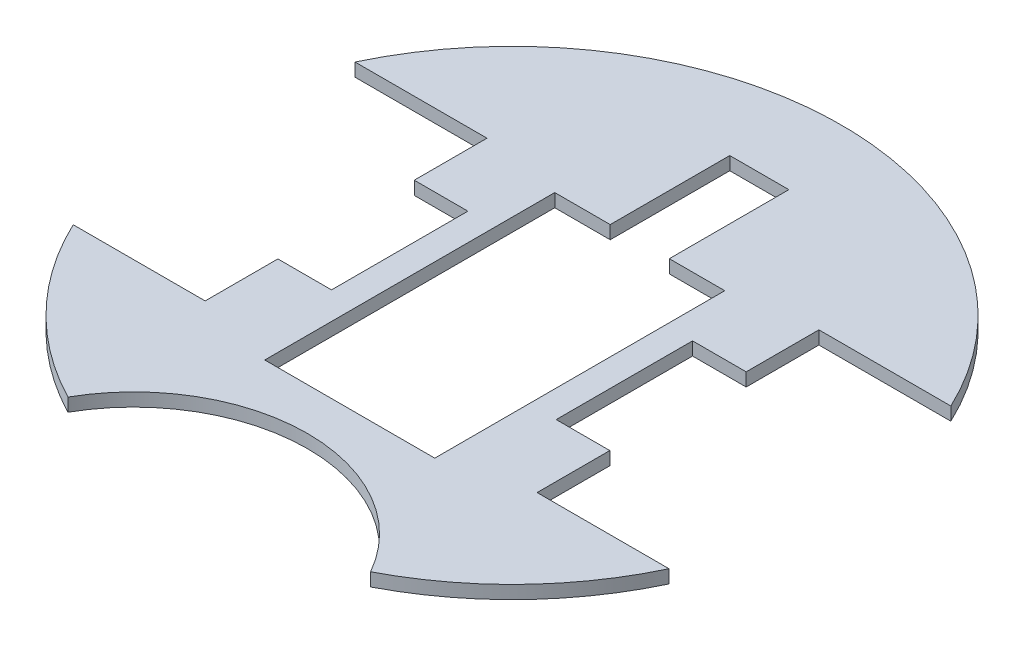
SolidWorks part; units mm, degrees
ref_plane "Front Plane" through (0, 0, 0) normal (0, 0, 1) x (1, 0, 0)
ref_plane "Top Plane" through (0, 0, 0) normal (0, 1, 0) x (1, 0, 0)
ref_plane "Right Plane" through (0, 0, 0) normal (1, 0, 0) x (0, 0, -1)
sketch "Sketch1" plane through (0, 0, 0) normal (0, 1, 0) x (1, 0, 0)
  line L0 (0, -83.2398) -> (-33.2911, -64.4046) construction
  line L1 (0, -83.2398) -> (0, 0) construction
  arc A0 (33.2911, -64.4046) -> (-33.2911, -64.4046) centre (0, 0) ccw
  arc A1 (33.2911, -64.4046) -> (-33.2911, -64.4046) centre (0, -83.2398) ccw
  dimension "D1" = 145
  dimension "D2" = 76.5
  dimension "D3" = 60.5
extrude "Boss-Extrude1" add sketch "Sketch1" along normal blind 2.9
sketch "solenoid placement" plane through (0, 2.9, 0) normal (0, 1, 0) x (1, 0, 0)
  line L4 (-18.7, -35.7) -> (18.7, -35.7)
  line L5 (18.7, -35.7) -> (18.7, 28.1)
  line L6 (18.7, 28.1) -> (-18.7, 28.1)
  line L7 (-18.7, 28.1) -> (-18.7, -35.7)
  line L8 (-18.7, -35.7) -> (18.7, -35.7)
  line L9 (18.7, -35.7) -> (18.7, 28.1)
  line L10 (18.7, 28.1) -> (-18.7, 28.1)
  line L11 (-18.7, 28.1) -> (-18.7, -35.7)
  circle A1 centre (0, 0) radius 72.5 construction
  arc A2 (33.2911, -64.4046) -> (-33.2911, -64.4046) centre (0, 0) ccw construction
  dimension "D1" = 0
extrude "Cut-Extrude1" cut sketch "solenoid placement" against normal through all
sketch "Sketch3" plane through (0, 2.9, 0) normal (0, 1, 0) x (1, 0, 0)
  line L0 (-36.51, -15) -> (-36.51, -31)
  line L1 (-24.71, 15) -> (-36.51, 15)
  line L2 (-24.71, 15) -> (-24.71, -15)
  line L3 (-24.71, -15) -> (-36.51, -15)
  line L4 (0, 0) -> (0, 72.5) construction
  line L5 (-36.51, -31) -> (-65.5382, -31)
  line L6 (-36.51, 15) -> (-36.51, 31)
  line L7 (-36.51, 31) -> (-65.5382, 31)
  line L8 (36.51, 31) -> (65.5382, 31)
  line L9 (36.51, 15) -> (36.51, 31)
  line L10 (36.51, -31) -> (65.5382, -31)
  line L11 (24.71, -15) -> (36.51, -15)
  line L12 (24.71, 15) -> (24.71, -15)
  line L13 (24.71, 15) -> (36.51, 15)
  line L14 (36.51, -15) -> (36.51, -31)
  arc A0 (33.2911, -64.4046) -> (-33.2911, -64.4046) centre (0, 0) ccw construction
  arc A1 (-65.5382, 31) -> (-65.5382, -31) centre (0, 0) ccw
  arc A2 (65.5382, 31) -> (65.5382, -31) centre (0, 0) cw
  dimension "D1" = 62
extrude "Cut-Extrude3" cut sketch "Sketch3" against normal through all
sketch "Sketch4" plane through (0, 2.9, 0) normal (0, 1, 0) x (1, 0, 0)
  line L0 (18.7, 28.1) -> (-18.7, 28.1) construction
  line L1 (-6.5, 28.1) -> (6.5, 28.1)
  line L2 (-6.5, 28.1) -> (-6.5, 54.4)
  line L3 (6.5, 54.4) -> (-6.5, 54.4) construction
  line L4 (6.5, 28.1) -> (6.5, 54.4)
  line L5 (6.5, 54.4) -> (-6.5, 54.4)
  point P6 (0, 28.1)
extrude "Cut-Extrude4" cut sketch "Sketch4" against normal through all
equation "\"smallPulleyTeeth\"= 15"
equation "\"largePulleyTeeth\"= 30"
equation "\"eighthThick\"= 2.9mm"
equation "\"sixteenthThick\" = 1.7mm"
equation "\"quarterThick\"=5.9mm"
equation "\"OD\" = 145mm"
equation "\"puckAngle\" = 60.5deg"
equation "\"D1@Sketch1\"=\"OD\""
equation "\"puckDiam\" = 76.5mm"
equation "\"D2@Sketch1\"=\"puckDiam\""
equation "\"D3@Sketch1\"=\"puckAngle\""
equation "\"D1@Boss-Extrude1\"=\"eighthThick\""
equation "\"axlePress\" = 5.9mm"
equation "\"press\" = 0.2mm"
equation "\"wheelClear\" = 0.3mm"
equation "\"10-32clear\" = 4.5mm"
equation "\"6-32clear\" = 3.3mm"
equation "\"8-32clear\" = 4.0mm"
equation "\"wheelHeight\" = 24mm"
equation "\"wheelWell\" = 62mm"
equation "\"D1@Sketch3\"=\"wheelWell\""
